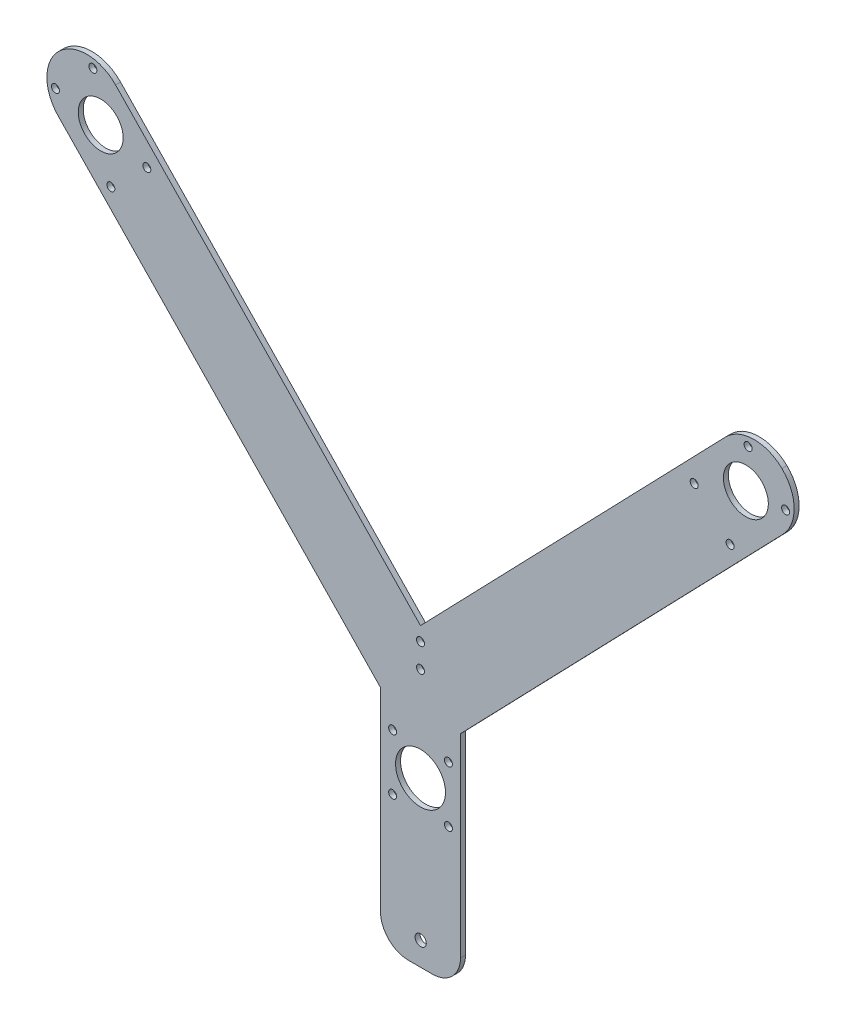
SolidWorks part; units mm, degrees
ref_plane "Front Plane" through (0, 0, 0) normal (0, 0, 1) x (1, 0, 0)
ref_plane "Top Plane" through (0, 0, 0) normal (0, 1, 0) x (1, 0, 0)
ref_plane "Right Plane" through (0, 0, 0) normal (1, 0, 0) x (0, 0, -1)
sketch "Sketch1" plane through (0, 0, 0) normal (0, 0, 1) x (1, 0, 0)
  line L0 (0, 0) -> (50.8, 0)
  line L1 (50.8, 0) -> (50.8, 141.3009)
  line L2 (50.8, 141.3009) -> (273.4748, 371.8874)
  line L3 (0, 0) -> (0, 141.3009)
  line L4 (0, 141.3009) -> (-222.6748, 371.8874)
  line L5 (-222.6748, 371.8874) -> (-186.1323, 407.1761)
  line L6 (-186.1323, 407.1761) -> (25.4, 188.1279)
  line L7 (25.4, 188.1279) -> (236.9323, 407.1761)
  line L8 (236.9323, 407.1761) -> (273.4748, 371.8874)
  circle A0 centre (25.4, 800.087) radius 406.4 construction
  point P3 (-80.3662, 297.652)
  dimension "D1" = 812.8
  dimension "D3" = 50.8
  dimension "D4" = 50.8
  dimension "D5" = 50.8
  dimension "D6" = 88
extrude "Boss-Extrude1" add sketch "Sketch1" along normal blind 3.175 contours L1 L2 L8 L7 L6 L5 L4 L3 L0
sketch "Sketch2" plane through (0, 0, 3.175) normal (0, 0, 1) x (1, 0, 0)
  line L0 (50.8, 141.3009) -> (273.4748, 371.8874) construction
  line L1 (-186.1323, 407.1761) -> (25.4, 188.1279) construction
  line L2 (236.9323, 407.1761) -> (273.4748, 371.8874) construction
  line L3 (-222.6748, 371.8874) -> (-186.1323, 407.1761) construction
  line L4 (50.8, 0) -> (50.8, 141.3009) construction
  line L5 (0, 0) -> (50.8, 0) construction
  line L11 (43.1292, 121.8692) -> (7.6708, 86.4108) construction
  line L12 (43.1292, 86.4108) -> (7.6708, 121.8692) construction
  circle A0 centre (232.2659, 365.7791) radius 14.2875
  circle A1 centre (-177.9371, 362.1249) radius 14.2875
  circle A2 centre (25.4, 104.14) radius 15.875
  circle A3 centre (43.1292, 121.8692) radius 2.54
  circle A4 centre (7.6708, 121.8692) radius 2.54
  circle A5 centre (7.6708, 86.4108) radius 2.54
  circle A6 centre (43.1292, 86.4108) radius 2.54
  dimension "D2" = 28.575
  dimension "D3" = 25.4
  dimension "D4" = 28.575
  dimension "D5" = 33.02
  dimension "D6" = 38.1
  dimension "D8" = 31.75
  dimension "D9" = 104.14
  dimension "D12" = 5.08
  dimension "D13" = 5.08
  dimension "D14" = 5.08
  dimension "D1" = 25.4
  dimension "D7" = 25.4
  dimension "D10" = 35.4584
  dimension "D11" = 35.4584
extrude "Cut-Extrude1" cut sketch "Sketch2" against normal through all
fillet "Fillet1" radius 25.4 4 edges at (273.4748, 371.8874, 1.5875) (236.9323, 407.1761, 1.5875) (-222.6748, 371.8874, 1.5875) (-186.1323, 407.1761, 1.5875)
sketch "Sketch7" plane through (0, 0, 0) normal (0, 0, -1) x (-1, 0, 0)
  circle A0 centre (-25.5077, 14.9496) radius 3.556
  dimension "D1" = 7.112
extrude "Cut-Extrude6" cut sketch "Sketch7" against normal through all contours A0
fillet "Fillet2" radius 17.78 1 edges at (0, 0, 1.5875)
fillet "Fillet3" radius 17.78 1 edges at (50.8, 0, 1.5875)
sketch "Sketch9" plane through (0, 0, 0) normal (0, 0, -1) x (-1, 0, 0)
  line L0 (-257.5429, 367.8521) -> (-222.2543, 331.3096) construction
  line L1 (-222.2543, 331.3096) -> (-199.4152, 353.365) construction
  line L2 (-199.4152, 353.365) -> (-233.6982, 390.8786) construction
  line L3 (-233.6982, 390.8786) -> (-257.5429, 367.8521) construction
  line L4 (-50.8, 141.3009) -> (-255.8305, 353.6162) construction
  circle A2 centre (-233.6982, 390.8786) radius 2.54
  circle A3 centre (-257.5429, 367.8521) radius 2.54
  circle A4 centre (-199.4152, 353.365) radius 2.54
  circle A5 centre (-222.2543, 331.3096) radius 2.54
  dimension "D2" = 50.8
  dimension "D4" = 31.75
  dimension "D1" = 31.75
  dimension "D3" = 15.875
extrude "Cut-Extrude7" cut sketch "Sketch9" against normal through all
ref_plane "Plane3" through (25.4, 0, 0) normal (-1, 0, 0) x (0, 0, 1)
mirror "Mirror3" about plane through (25.4, 0, 0) normal (-1, 0, 0) of "Cut-Extrude7"
sketch "Sketch10" plane through (0, 0, 0) normal (0, 0, -1) x (-1, 0, 0)
  line L0 (-25.4, 188.1279) -> (-25.4, 0) construction
  line L1 (-17.78, 0) -> (-33.02, 0) construction
  circle A0 centre (-25.4, 164.0639) radius 2.54
  circle A1 centre (-25.4, 179.3039) radius 2.54
  dimension "D1" = 5.08
  dimension "D2" = 15.24
  dimension "D3" = 15.24
extrude "Cut-Extrude8" cut sketch "Sketch10" against normal through all contours A1 | A0
